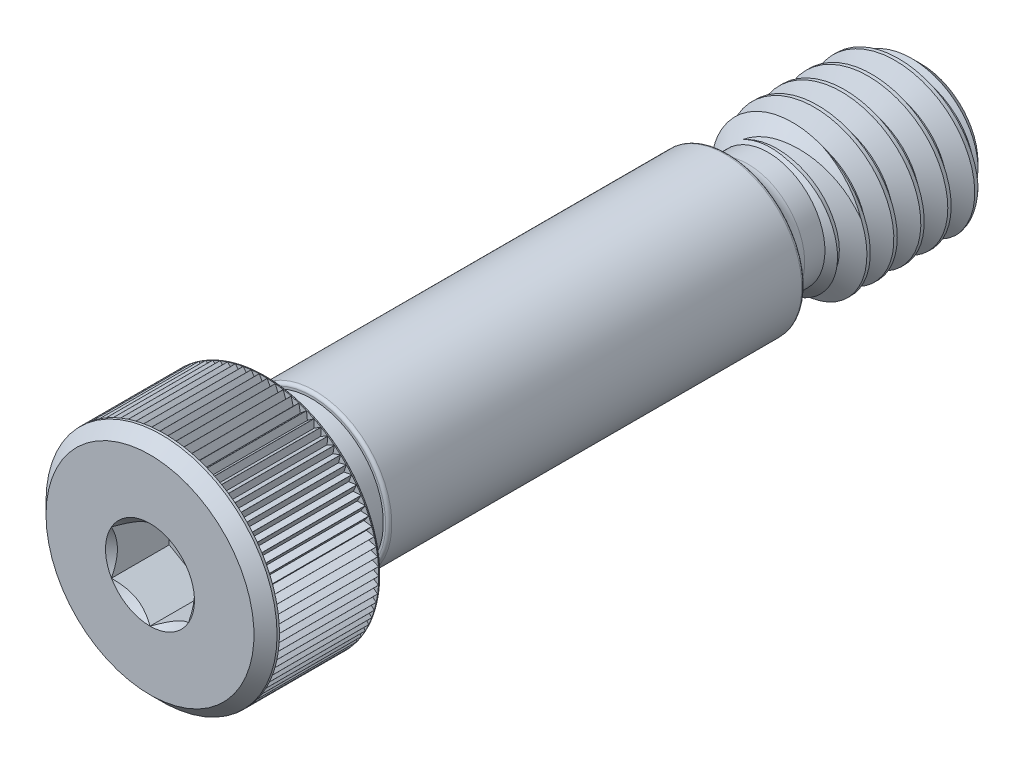
SolidWorks part; units mm, degrees
other "DetailItem1"
other "DetailItem2"
other "DetailItem5"
other "DetailItem6"
ref_plane "Front" through (0, 0, 0) normal (0, 0, 1) x (1, 0, 0)
ref_plane "Top" through (0, 0, 0) normal (0, 1, 0) x (1, 0, 0)
ref_plane "Right" through (0, 0, 0) normal (1, 0, 0) x (0, 0, -1)
sketch "Sketch1" plane through (0, 0, 0) normal (1, 0, 0) x (0, 0, -1)
  line L7 (-10.0125, 0) -> (10.0125, 0) construction
  line L8 (10.0125, 1.475) -> (9.4875, 2)
  line L9 (9.9687, 2.0758) -> (10.3187, 1.4696) construction
  line L16 (10.3187, 1.4696) -> (10.6687, 2.0758) construction
  line L22 (10.0125, 2) -> (10.0125, 0)
  line L23 (-7.0125, 3) -> (-7.0125, 1.86)
  line L24 (-7.0125, 1.86) -> (-5.8125, 1.86)
  line L25 (10.6687, 2.0758) -> (9.9687, 2.0758) construction
  line L26 (5.5125, 1.475) -> (6.0375, 1.475)
  line L27 (6.0375, 1.475) -> (6.5625, 2)
  line L29 (-10.0125, 3) -> (-10.0125, 0)
  line L30 (-10.0125, 3) -> (-7.0125, 3)
  line L33 (-5.8125, 2) -> (-5.8125, 1.86)
  line L34 (-5.8125, 2) -> (4.9875, 2)
  line L35 (10.0125, 2) -> (6.5625, 2)
  line L37 (9.9906, 2.0379) -> (10.6469, 2.0379)
  line L38 (10.6469, 2.0379) -> (10.3625, 1.5453)
  line L39 (10.3625, 1.5453) -> (10.275, 1.5453)
  line L40 (10.275, 1.5453) -> (9.9906, 2.0379)
  line L41 (10.3187, 1.5453) -> (10.3187, 1.4696) construction
  line L42 (10.0125, 2) -> (10.625, 2) construction
  line L47 (10.3188, 2.0758) -> (10.3187, 2) construction
  line L48 (4.9875, 2) -> (5.5125, 2) construction
  line L49 (-9.7125, 3) -> (-10.0125, 2.7)
  line L50 (10.0125, -2) -> (6.5625, -2)
  line L51 (-9.6525, 3) -> (-9.6525, 2.7) construction
  line L52 (-9.6525, 2.7) -> (-7.0725, 2.7) construction
  line L53 (-8.3625, 2.7) -> (-8.3625, 3) construction
  arc A0 (4.9875, 2) -> (5.5125, 1.475) centre (5.5125, 2) ccw
  arc A1 (4.9128, 2) -> (4.9921, 1.9306) centre (4.9128, 1.92) cw
  arc A2 (-5.8125, 1.92) -> (-5.7325, 2) centre (-5.7325, 1.92) cw
  arc A4 (-7.0725, 3) -> (-7.0125, 2.94) centre (-7.0725, 2.94) cw
  point P2 (0, 0)
  point P20 (10.3187, 2.0379)
  point P44 (-8.3625, 3)
  point P45 (10.0125, 2)
  point P46 (-9.6525, 3)
  point P47 (-7.0125, 2.43)
  point P48 (6.0375, 2.43)
  point P51 (-8.5125, 0)
  point P52 (8.6125, 2)
  point P54 (10.0125, 2.43)
  point P57 (10.0125, -2.43)
  point P58 (6.0375, -2.43)
  dimension "D6" = 0.08
  dimension "D8" = 0.06
  dimension "D1" = 45
  dimension "Pitch" = 0.7
  dimension "D3" = 0.0875
  dimension "D2" = 0.525
  dimension "D4" = 3.72
  dimension "D5" = 1.2
  dimension "D9" = 0.3
  dimension "D12" = 0.06
  dimension "D10" = 1.4
  dimension "D11" = 1.5
  dimension "Shoulder Diameter" = 4
  dimension "Thread Length" = 4.5
sketch "Sketch2" plane through (0, 0, 0) normal (0, 0, 1) x (1, 0, 0)
  line L9 (0, 1.1547) -> (-1, 0.5774)
  line L11 (-0.1048, 3) -> (0.1048, 3)
  line L12 (0.1048, 3) -> (0, 2.8185)
  line L13 (0, 2.8185) -> (-0.1048, 3)
  line L14 (0, 0) -> (-0.1048, 3) construction
  line L15 (0, 0) -> (0.1048, 3) construction
  line L16 (-1, 0.5774) -> (-1, -0.5774)
  line L17 (-1, -0.5774) -> (0, -1.1547)
  line L18 (0, -1.1547) -> (1, -0.5774)
  line L19 (1, -0.5774) -> (1, 0.5774)
  line L20 (1, 0.5774) -> (0, 1.1547)
  circle A0 centre (0, 0) radius 1 construction
  circle A2 centre (0, 0) radius 3
sketch "Sketch12" plane through (0, 0, 0) normal (1, 0, 0) x (0, 0, -1)
  line L0 (-10.0125, 0) -> (-10.0125, 2.7)
  line L1 (-10.0125, 2.7) -> (-9.7125, 3)
  line L2 (-9.7125, 3) -> (-7.0725, 3)
  line L3 (10.0125, 1.475) -> (9.4875, 2) construction
  line L5 (6.0375, 1.475) -> (6.5625, 2) construction
  line L7 (5.5125, 1.475) -> (6.0375, 1.475) construction
  line L8 (10.0125, 1.475) -> (9.4875, 2)
  line L9 (6.0375, 1.475) -> (6.5625, 2)
  line L11 (5.5125, 1.475) -> (6.0375, 1.475)
  line L12 (-7.0125, 1.86) -> (-7.0125, 2.94)
  line L13 (-7.0125, 1.86) -> (-5.8125, 1.86)
  line L14 (-5.8125, 1.86) -> (-5.8125, 1.92)
  line L15 (-5.7325, 2) -> (4.9128, 2)
  line L16 (6.5625, 2) -> (9.4875, 2)
  line L17 (10.0125, 1.475) -> (10.0125, 0)
  line L18 (10.0125, 0) -> (-10.0125, 0)
  arc A0 (-7.0125, 2.94) -> (-7.0725, 3) centre (-7.0725, 2.94) ccw construction
  arc A1 (-7.0125, 2.94) -> (-7.0725, 3) centre (-7.0725, 2.94) ccw
  arc A5 (4.9875, 2) -> (5.5125, 1.475) centre (5.5125, 2) ccw construction
  arc A6 (4.9921, 1.9306) -> (4.9128, 2) centre (4.9128, 1.92) ccw construction
  arc A7 (-5.7325, 2) -> (-5.8125, 1.92) centre (-5.7325, 1.92) ccw construction
  arc A8 (4.9921, 1.9306) -> (5.5125, 1.475) centre (5.5125, 2) ccw
  arc A9 (4.9921, 1.9306) -> (4.9128, 2) centre (4.9128, 1.92) ccw
  arc A10 (-5.7325, 2) -> (-5.8125, 1.92) centre (-5.7325, 1.92) ccw
revolve "Revolve1" add sketch "Sketch12" angle 360 mid plane about L18
sketch "Sketch8" plane through (0, 0, 10.0125) normal (0, 0, 1) x (1, 0, 0)
  line L6 (0, -1.1547) -> (1, -0.5774) construction
  line L7 (-1, -0.5774) -> (0, -1.1547) construction
  line L8 (-1, 0.5774) -> (-1, -0.5774) construction
  line L9 (0, 1.1547) -> (-1, 0.5774) construction
  line L10 (1, 0.5774) -> (0, 1.1547) construction
  line L11 (1, -0.5774) -> (1, 0.5774) construction
  line L12 (0, -1.1547) -> (1, -0.5774)
  line L13 (-1, -0.5774) -> (0, -1.1547)
  line L14 (-1, 0.5774) -> (-1, -0.5774)
  line L15 (0, 1.1547) -> (-1, 0.5774)
  line L16 (1, 0.5774) -> (0, 1.1547)
  line L17 (1, -0.5774) -> (1, 0.5774)
extrude "Cut-Extrude2" cut sketch "Sketch8" against normal up to vertex (1.5 mm away) up to point (0, 0, 8.5125)
sketch "Sketch9" plane through (0, 0, 10.0125) normal (0, 0, 1) x (1, 0, 0)
  circle A1 centre (0, 0) radius 1.1547
extrude "Cut-Extrude4" cut sketch "Sketch9" against normal up to vertex (1.5 mm away) draft 45 up to point (0, 0, 8.5125)
ref_axis "Center Axis1" through (0, 0, -14.7909) along (0, 0, 1)
ref_plane "Contact Plane1" through (0, 0, -10.0125) normal (0, 0, 1) x (1, 0, 0)
ref_plane "Contact Plane2" through (0, 0, 7.0125) normal (0, 0, 1) x (1, 0, 0)
ref_plane "Plane2" through (0, 0, -6.0375) normal (0, 0, -1) x (-1, 0, 0)
split "Split1" trim tools "Plane2" bodies to split 118 resulting bodies 122 123
sketch "Sketch3" plane through (0, 0, -10.0125) normal (0, 0, 1) x (1, 0, 0)
  circle A0 centre (0, 0) radius 2 construction
  circle A2 centre (0, 0) radius 2
curve "Helix/Spiral1" pitch 0.7 height 4.5 radius 2 centre (0, 0, -10.0125) axis (0, 0, 1) start towards (0, 1, 0)
sketch "Sketch13" plane through (0, 0, 0) normal (1, 0, 0) x (0, 0, -1)
  line L0 (9.9906, 2.0379) -> (10.6469, 2.0379) construction
  line L1 (10.275, 1.5453) -> (9.9906, 2.0379) construction
  line L2 (10.3625, 1.5453) -> (10.275, 1.5453) construction
  line L3 (10.6469, 2.0379) -> (10.3625, 1.5453) construction
  line L16 (9.9906, 2.0379) -> (10.6469, 2.0379)
  line L17 (10.275, 1.5453) -> (9.9906, 2.0379)
  line L18 (10.3625, 1.5453) -> (10.275, 1.5453)
  line L19 (10.6469, 2.0379) -> (10.3625, 1.5453)
sweep "Cut-Sweep1" cut profiles "Sketch13" path "Helix/Spiral1" align with end faces yes
combine bodies "Combine1" operation type add bodies to combine 123 126
ref_plane "Plane1" through (0, 0, 9.6525) normal (0, 0, 1) x (1, 0, 0)
sketch "Sketch11" plane through (0, 0, 9.6525) normal (0, 0, 1) x (1, 0, 0)
  line L0 (0.1048, 3) -> (0, 2.8185) construction
  line L1 (0, 2.8185) -> (-0.1048, 3) construction
  line L2 (-0.1048, 3) -> (0.1048, 3) construction
  line L3 (0.1048, 3) -> (0, 2.8185)
  line L4 (0, 2.8185) -> (-0.1048, 3)
  line L5 (-0.1048, 3) -> (0.1048, 3)
  point P3 (0, 0.0018)
  point P8 (2.3908, 0.7309)
extrude "Cut-Extrude5" cut sketch "Sketch11" against normal up to vertex (2.58 mm away) up to point (0, 2.7, 7.0725)
pattern_circular "CirPattern1" count 90 over 360 about axis through (0, 0, 9.7125) along (0, 0, -1) of "Cut-Extrude5"
equation "\"D3@Sketch1\"=\"Pitch@Sketch1\"/8"
equation "\"D2@Sketch1\"=\"Pitch@Sketch1\"*.75"
equation "\"D4@Sketch1\"=\"Shoulder Diameter@Sketch1\"*.93"
equation "\"D5@Sketch1\"=\"Shoulder Length@Sketch1\"*.1"
equation "\"D6@Sketch1\"=\"Shoulder Diameter@Sketch1\"*.04*0.5"
equation "\"D8@Sketch1\"=\"Head Height@Sketch1\"*.02"
equation "\"D9@Sketch1\"=\"Head Height@Sketch1\"*.1"
equation "\"D4@Helix/Spiral1\"=\"Pitch@Sketch1\""
equation "\"D3@Helix/Spiral1\"=\"Thread Length@Sketch1\""
equation "\"D1@CirPattern1\" = 360 / \"Knurl Angle@Sketch2\""
equation "\"D12@Sketch1\"=\"Head Height@Sketch1\"*.02"
equation "\"D10@Sketch1\"=\"Pitch@Sketch1\"*2"
equation "\"D11@Sketch1\"=\"Head Height@Sketch1\"*0.5"
